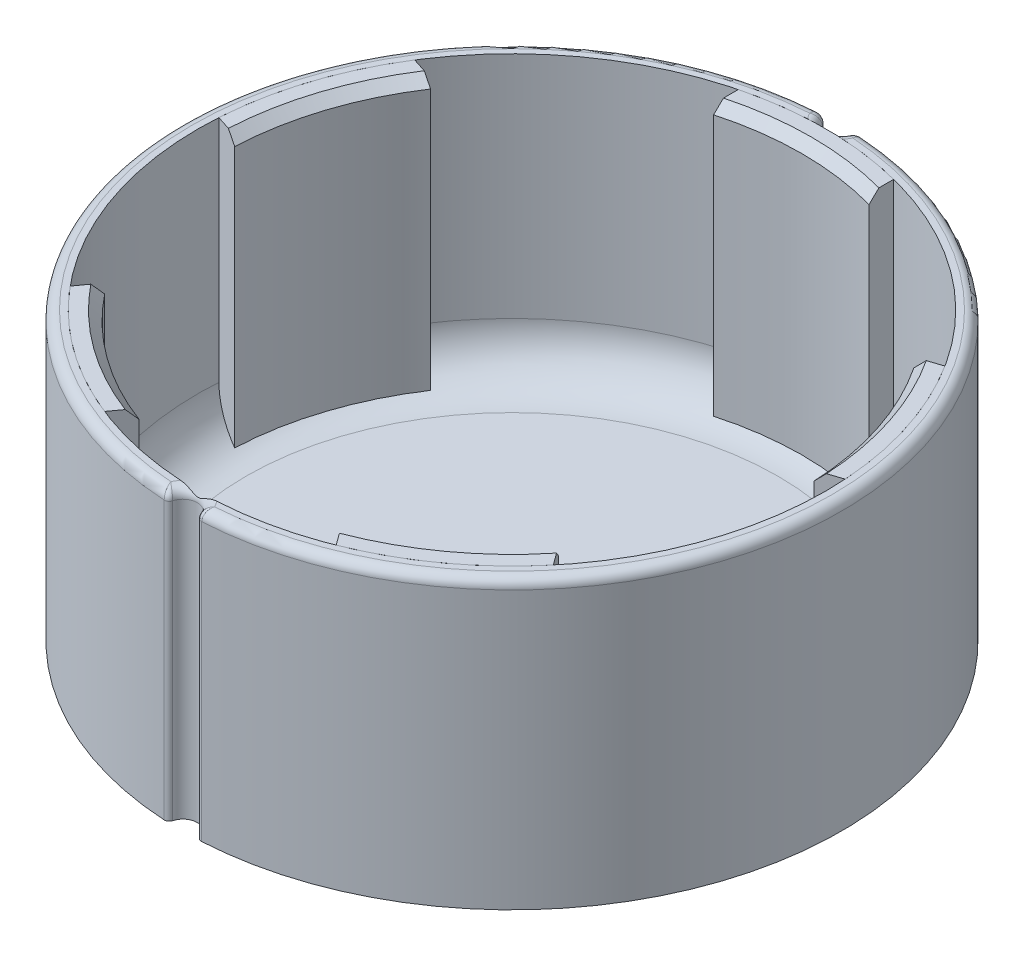
SolidWorks part; units mm, degrees
other "Markup1"
sketch "Sketch4"
other "Markup5"
sketch "Sketch8" plane through (34.5, 25, 34.4428) normal (0.0041, 0.9851, 0.1719) x (0.981, -0.0374, 0.1906)
other "Markup6"
sketch "Sketch9" plane through (34.5, 25, 34.4428) normal (0.0041, 0.9851, 0.1719) x (0.981, -0.0374, 0.1906)
other "Markup7"
sketch "Sketch10" plane through (-34.5, 25, 34.4428) normal (-0.125, 0.9874, 0.0969) x (0.5933, -0.0039, 0.805)
ref_plane "Front Plane" through (0, 0, 0) normal (0, 0, 1) x (1, 0, 0)
ref_plane "Top Plane" through (0, 0, 0) normal (0, 1, 0) x (1, 0, 0)
ref_plane "Right Plane" through (0, 0, 0) normal (1, 0, 0) x (0, 0, -1)
sketch "Sketch1" plane through (0, 0, 0) normal (0, 1, 0) x (1, 0, 0)
  line L3 (0, 0.002) -> (0, 3.7877) construction
  line L4 (0, 3.7877) -> (2.417, 3.7877)
  line L5 (0, 3.7877) -> (-2.417, 3.7877)
  arc A0 (1.9642, -34.442) -> (34.1982, 4.5552) centre (0, 0.002) ccw
  arc A2 (-2.417, 3.7877) -> (2.417, 3.7877) centre (0, 0.002) ccw
  circle A3 centre (0, 0.002) radius 34.5 construction
  arc A7 (-1.3541, 33.8562) -> (1.3541, 33.8562) centre (0, 34.5015) ccw
  arc A8 (34.1982, 4.5552) -> (2.3241, 34.4236) centre (0, 0.002) ccw
  arc A9 (-2.3241, 34.4236) -> (-34.1982, 4.5552) centre (0, 0.002) ccw
  arc A10 (-34.1982, 4.5552) -> (-1.9642, -34.442) centre (0, 0.002) ccw
  arc A11 (1.3541, 33.8562) -> (2.3241, 34.4236) centre (2.2568, 33.4259) cw
  arc A12 (-1.3541, 33.8562) -> (-2.3241, 34.4236) centre (-2.2568, 33.4259) ccw
  arc A13 (1.4518, -34.0686) -> (-1.4518, -34.0686) centre (0, -34.4457) ccw
  arc A14 (1.4518, -34.0686) -> (1.9642, -34.442) centre (1.9358, -33.9428) ccw
  arc A15 (-1.4518, -34.0686) -> (-1.9642, -34.442) centre (-1.9358, -33.9428) cw
  point P15 (1.4997, 34.4694)
  dimension "D2" = 4.834
  dimension "D3" = 4.4915
  dimension "D4" = 34.5
  dimension "D5" = 1
  dimension "D6" = 1.5
  dimension "D7" = 0.5
  dimension "D11" = 1.4997
sketch "Sketch2" plane through (0, 0, 0) normal (0, 1, 0) x (1, 0, 0)
  line L0 (0, 32.85) -> (0, 30.35) construction
  line L1 (-8.1359, 31.8266) -> (0, 32.85) construction
  line L2 (0, 32.85) -> (8.1359, 31.8266) construction
  line L3 (-8.1359, 31.8266) -> (-8.1359, 29.2392)
  line L6 (8.1359, 29.2392) -> (8.1359, 31.8266)
  circle A16 centre (0, 0) radius 32.85
  arc A18 (-8.1359, 29.2392) -> (8.1359, 29.2392) centre (0, 0) cw
  point P3 (0, 30.35)
  dimension "D1" = 65.7
  dimension "D2" = 8.2
  dimension "D3" = 2.5
extrude "Boss-Extrude1" add sketch "Sketch1" along normal blind 30 contours A10 A0 A8 A7 A9 A2 L5 L4 | L5 A2 L4 region at (0, 0, 0.1522) region at (2.2155, 0, 33.5591)
extrude "Cut-Extrude2" cut sketch "Sketch2" along normal up to next from offset 1 contours A16 | A16 region at (0, 0, 0.3838)
extrude "Boss-Extrude2" add sketch "Sketch2<2>" along normal up to surface (30 mm away) separate body contours A16 region at (0, 0, -31.2435) up to face at (0, 30, 32.85)
sketch "Sketch2<2>" plane through (0, 0, 0) normal (0, 1, 0) x (1, 0, 0) same geometry as "Sketch2"
chamfer "Chamfer2" distance 1 angle 45 1 edges at (0, 30, -30.35)
pattern_circular "CirPattern2" count 5 over 360 about axis through (0, 30, 0) along (0, 1, 0) of bodies 106
fillet "Fillet1" radius 1 8 edges at (-1.7518, 30, -34.2891) (0, 30, -33.0015) (1.7518, 30, -34.2891) (34.4995, 30, 0.1783) (1.6412, 30, 34.3469) (0, 30, 32.9457) (-1.6412, 30, 34.3469) (-34.4995, 30, 0.1783)
fillet "Fillet5" radius 5 1 edges at (0, 1, 32.85)
sketch "Sketch11" plane through (0, 30, 0) normal (0, 1, 0) x (1, 0, 0)
  arc A0 (8.1359, 31.8266) -> (27.7547, 17.5726) centre (0, 0) cw
